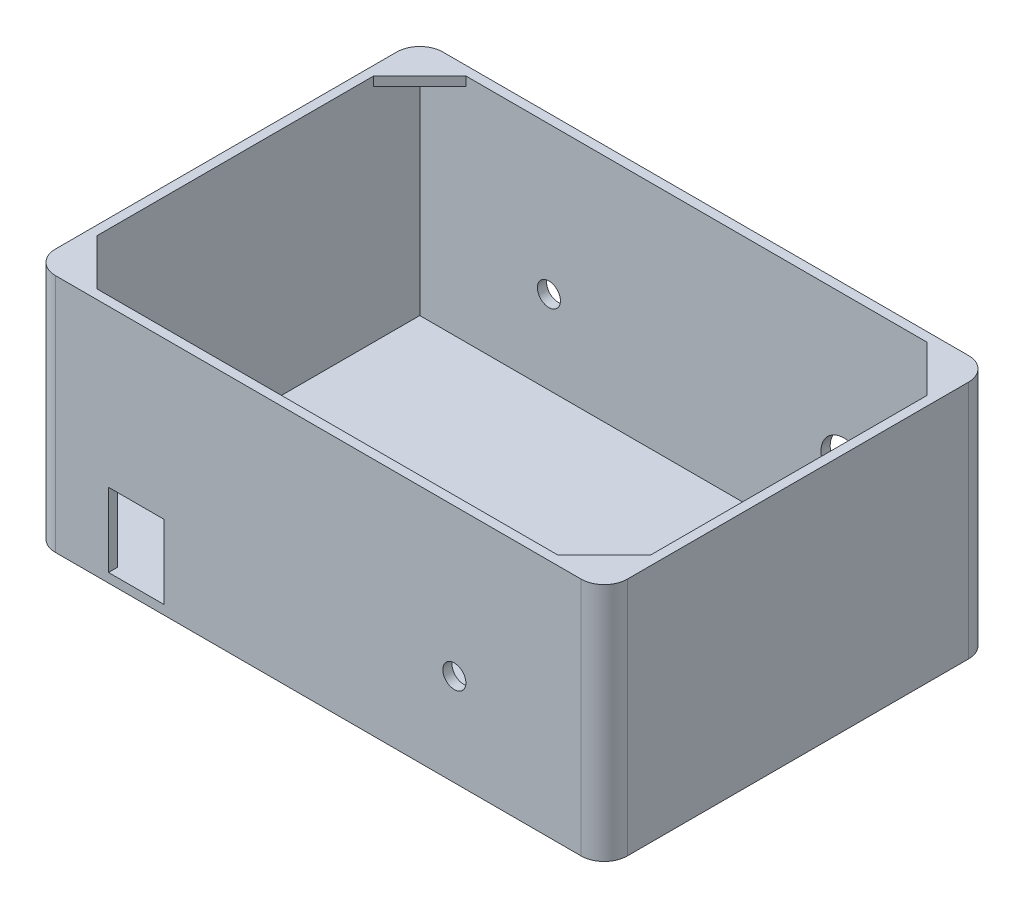
SolidWorks part; units mm, degrees
ref_plane "Front Plane" through (0, 0, 0) normal (0, 0, 1) x (1, 0, 0)
ref_plane "Top Plane" through (0, 0, 0) normal (0, 1, 0) x (1, 0, 0)
ref_plane "Right Plane" through (0, 0, 0) normal (1, 0, 0) x (0, 0, -1)
sketch "Sketch1" plane through (0, 0, 0) normal (0, 1, 0) x (1, 0, 0)
  line L0 (-62, 42) -> (-62, -42)
  line L1 (-60, 40) -> (60, 40)
  line L2 (-60, 40) -> (-60, -40)
  line L3 (-60, -40) -> (60, -40)
  line L4 (60, 40) -> (60, -40)
  line L5 (-60, 40) -> (60, -40) construction
  line L6 (-60, -40) -> (60, 40) construction
  line L7 (-62, -42) -> (62, -42)
  line L8 (62, 42) -> (62, -42)
  line L9 (-62, 42) -> (62, 42)
  point P0 (0, 0)
  dimension "D1" = 120
  dimension "D2" = 80
  dimension "D3" = 2
extrude "Boss-Extrude1" add sketch "Sketch1" along normal blind 2 contours L2 L1 L4 L3
extrude "Boss-Extrude2" add sketch "Sketch1<3>" along normal blind 52
sketch "Sketch1<3>" plane through (0, 0, 0) normal (0, 1, 0) x (1, 0, 0) same geometry as "Sketch1"
sketch "Sketch2" plane through (0, 0, 42) normal (0, 0, 1) x (1, 0, 0)
  line L0 (-45.5, 2) -> (-45.5, 18)
  line L1 (-45.5, 18) -> (-33.5, 18)
  line L2 (-33.5, 18) -> (-33.5, 2)
  line L3 (-33.5, 2) -> (-45.5, 2)
  line L4 (-62, 0) -> (62, 0) construction
  line L5 (-62, 52) -> (-62, 0) construction
  dimension "D1" = 12
  dimension "D2" = 16
  dimension "D3" = 2
  dimension "D4" = 16.5
extrude "Cut-Extrude1" cut sketch "Sketch2" against normal blind 2
sketch "Sketch3" plane through (0, 0, 42) normal (0, 0, 1) x (1, 0, 0)
  line L0 (62, 52) -> (62, 0) construction
  line L1 (-62, 0) -> (62, 0) construction
  circle A0 centre (29.5, 20) radius 2.5
  dimension "D1" = 5
  dimension "D2" = 32.5
  dimension "D3" = 20
extrude "Cut-Extrude3" cut sketch "Sketch3" against normal blind 2
sketch "Sketch5" plane through (0, 0, -42) normal (0, 0, -1) x (-1, 0, 0)
  line L0 (-62, 0) -> (62, 0) construction
  line L1 (-62, 52) -> (-62, 0) construction
  line L2 (62, 52) -> (62, 0) construction
  circle A0 centre (-32, 20) radius 5
  circle A1 centre (32, 20) radius 2.5
  dimension "D1" = 10
  dimension "D2" = 5
  dimension "D5" = 30
  dimension "D3" = 20
  dimension "D4" = 20
  dimension "D6" = 30
extrude "Cut-Extrude6" cut sketch "Sketch5" against normal blind 2
fillet "Fillet1" radius 5 1 edges at (62, 26, -42)
fillet "Fillet2" radius 5 1 edges at (62, 26, 42)
fillet "Fillet3" radius 5 1 edges at (-62, 26, -42)
fillet "Fillet4" radius 5 1 edges at (-62, 26, 42)
ref_plane "Plane1" through (0, 52, 0) normal (0, 1, 0) x (1, 0, 0)
sketch "Sketch6" plane through (0, 52, 0) normal (0, 1, 0) x (1, 0, 0)
  line L0 (-50, 40) -> (-60, 30)
  line L1 (-60, 40) -> (60, 40) construction
  line L2 (-60, 40) -> (-60, -40) construction
  line L3 (-60, 30) -> (-60, 40)
  line L4 (-60, 40) -> (-50, 40)
  line L5 (-1064.5629, -14.8201) -> (48935.4371, -14.8201) construction
  line L6 (-1000, 0) -> (49000, 0) construction
  line L7 (0, -1000) -> (0, 49000) construction
  line L8 (-60, -30) -> (-60, -40)
  line L9 (-50, -40) -> (-60, -30)
  line L10 (-60, -40) -> (-50, -40)
  line L11 (0, 1000) -> (0, -49000) construction
  line L12 (50, -40) -> (60, -30)
  line L13 (60, -40) -> (50, -40)
  line L14 (60, -30) -> (60, -40)
  line L15 (60, 30) -> (60, 40)
  line L16 (50, 40) -> (60, 30)
  line L17 (60, 40) -> (50, 40)
  dimension "D1" = 10
  dimension "D2" = 10
extrude "Boss-Extrude3" add sketch "Sketch6" against normal blind 2
